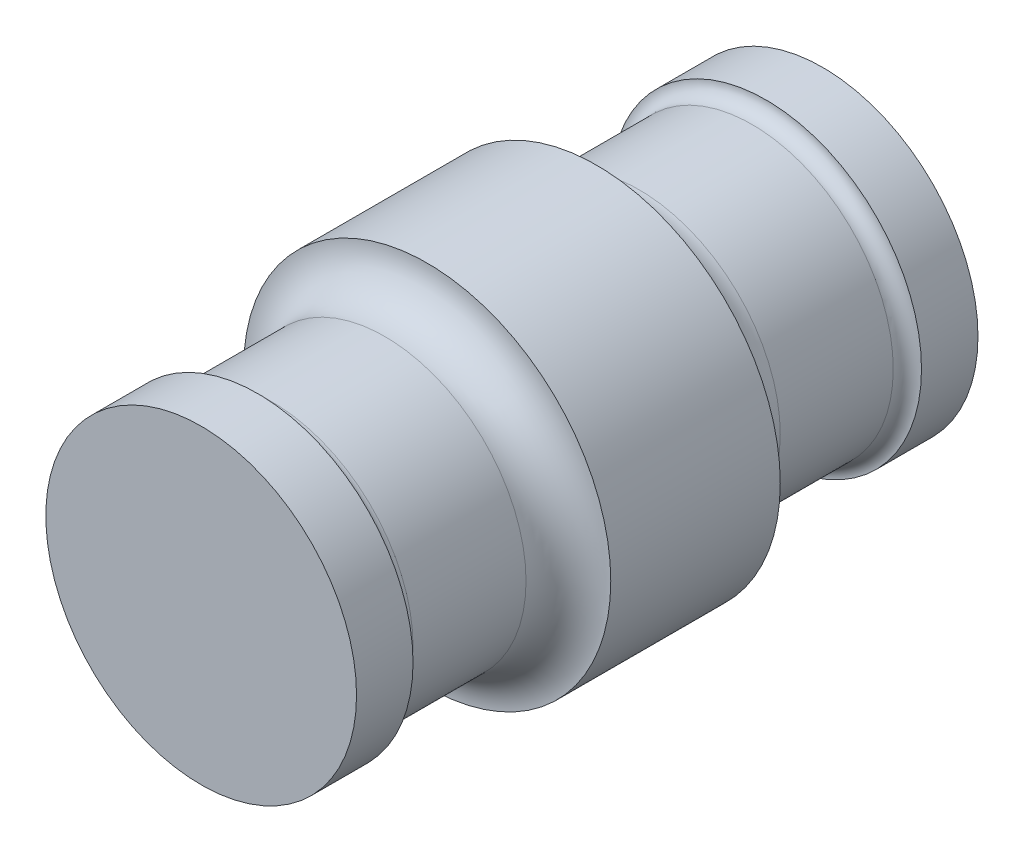
SolidWorks part; units mm, degrees
ref_plane "Front Plane" through (0, 0, 0) normal (0, 0, 1) x (1, 0, 0)
ref_plane "Top Plane" through (0, 0, 0) normal (0, 1, 0) x (1, 0, 0)
ref_plane "Right Plane" through (0, 0, 0) normal (1, 0, 0) x (0, 0, -1)
sketch "Sketch1" plane through (0, 0, 0) normal (0, 0, 1) x (1, 0, 0)
  circle A0 centre (0, 0) radius 5
  circle A1 centre (0, 0) radius 6.5
  dimension "D1" = 10
  dimension "D2" = 13
extrude "Boss-Extrude1" add sketch "Sketch1" along normal blind 6 contours A0 region at (0, 0, 0)
extrude "Boss-Extrude2" add sketch "Sketch1<3>" against normal blind 6 contours A1 A0 | A0 region at (0, 0, 0) region at (-6.3162, 0, 0)
sketch "Sketch1<3>" plane through (0, 0, 0) normal (0, 0, 1) x (1, 0, 0) same geometry as "Sketch1"
extrude "Boss-Extrude3" add sketch "Sketch1<4>" against normal blind 12 contours A0 region at (0, 0, 0)
sketch "Sketch1<4>" plane through (0, 0, 0) normal (0, 0, 1) x (1, 0, 0) same geometry as "Sketch1"
fillet "Fillet1" radius 1.5 2 edges at (5, 0, 0) (5, 0, -6)
sketch "Sketch2" plane through (0, 0, 6) normal (0, 0, 1) x (1, 0, 0)
  circle A0 centre (0, 0) radius 1.6
  dimension "D1" = 3.2
extrude "Cut-Extrude1" [suppressed] cut sketch "Sketch2" against normal through all both and the other way through all
sketch "Sketch3" plane through (0, 0, 6) normal (0, 0, 1) x (1, 0, 0)
  circle A0 centre (0, 0) radius 5.5
  circle A1 centre (0, 0) radius 5 construction
  dimension "D1" = 0.5
extrude "Boss-Extrude4" add sketch "Sketch3" along normal blind 2
extrude "Boss-Extrude5" add sketch "Sketch3<2>" against normal blind 2 from offset 18 offset against normal yes
sketch "Sketch3<2>" plane through (0, 0, 6) normal (0, 0, 1) x (1, 0, 0) same geometry as "Sketch3"
fillet "Fillet2" radius 0.5 2 edges at (5, 0, 6) (5, 0, -12)
fillet "Fillet3" [suppressed] radius 0.5
